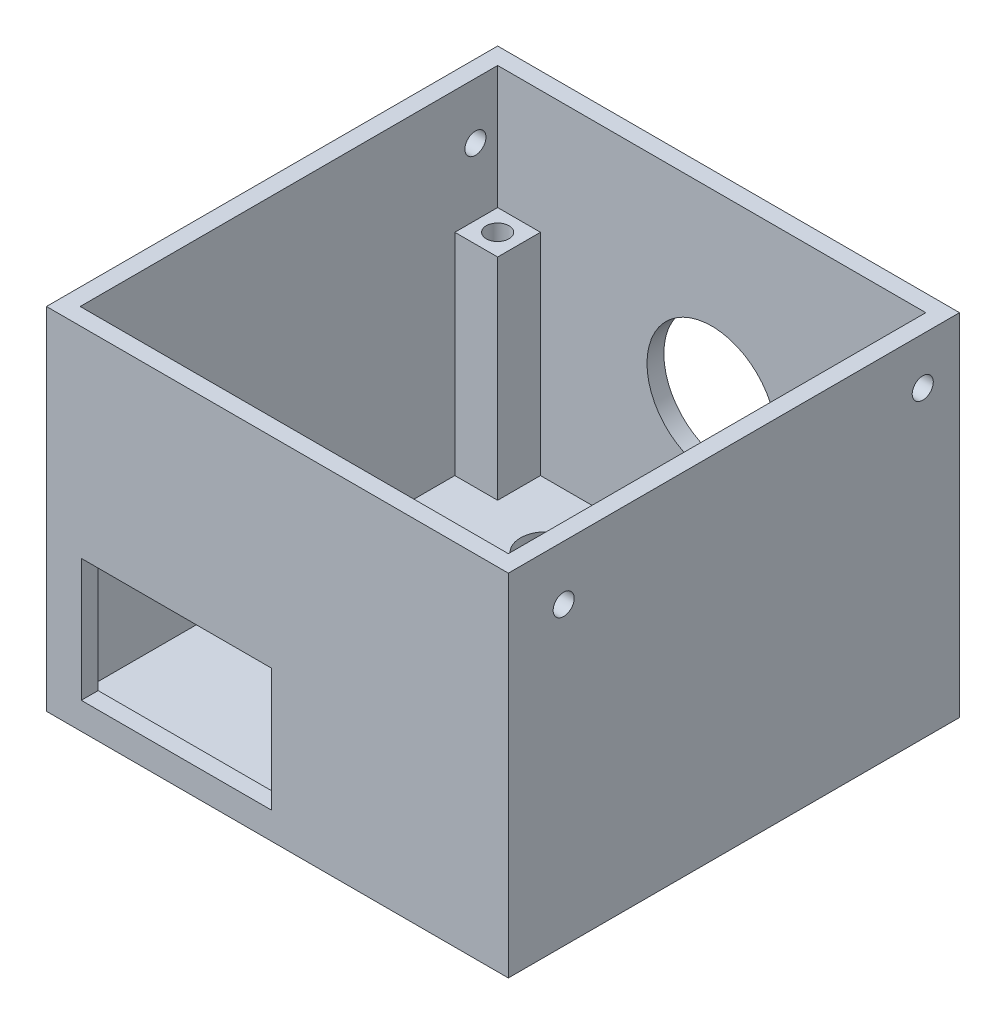
SolidWorks part; units mm, degrees
ref_plane "Front Plane" through (0, 0, 0) normal (0, 0, 1) x (1, 0, 0)
ref_plane "Top Plane" through (0, 0, 0) normal (0, 1, 0) x (1, 0, 0)
ref_plane "Right Plane" through (0, 0, 0) normal (1, 0, 0) x (0, 0, -1)
sketch "Sketch1" plane through (0, 0, 0) normal (0, 1, 0) x (1, 0, 0)
  line L1 (27.4, -26.765) -> (-27.4, -26.765)
  line L2 (27.4, -26.765) -> (27.4, 26.765)
  line L3 (27.4, 26.765) -> (-27.4, 26.765)
  line L4 (-27.4, -26.765) -> (-27.4, 26.765)
  line L5 (27.4, -26.765) -> (-27.4, 26.765) construction
  line L6 (27.4, 26.765) -> (-27.4, -26.765) construction
  point P0 (0, 0)
  dimension "D1" = 54.8
  dimension "D2" = 53.53
extrude "Boss-Extrude1" add sketch "Sketch1" along normal blind 41.6
sketch "Sketch2" plane through (0, 41.6, 0) normal (0, 1, 0) x (1, 0, 0)
  line L0 (-27.4, 26.765) -> (-27.4, -26.765) construction
  line L1 (25.4, -24.765) -> (-25.4, -24.765)
  line L2 (25.4, -24.765) -> (25.4, 24.765)
  line L3 (25.4, 24.765) -> (-25.4, 24.765)
  line L4 (-25.4, -24.765) -> (-25.4, 24.765)
  line L5 (25.4, -24.765) -> (-25.4, 24.765) construction
  line L6 (25.4, 24.765) -> (-25.4, -24.765) construction
  line L7 (27.4, 26.765) -> (-27.4, 26.765) construction
  point P0 (0, 0)
  dimension "D1" = 2
  dimension "D2" = 2
extrude "Cut-Extrude1" cut sketch "Sketch2" against normal blind 39.6
sketch "Sketch3" plane through (0, 2, 0) normal (0, 1, 0) x (1, 0, 0)
  line L1 (-25.4, 24.765) -> (-20.32, 24.765)
  line L2 (-25.4, 24.765) -> (-25.4, 19.685)
  line L3 (-25.4, 19.685) -> (-20.32, 19.685)
  line L4 (-20.32, 24.765) -> (-20.32, 19.685)
  line L5 (25.4, 24.765) -> (20.32, 24.765)
  line L6 (25.4, 24.765) -> (25.4, 19.685)
  line L7 (25.4, 19.685) -> (20.32, 19.685)
  line L8 (20.32, 24.765) -> (20.32, 19.685)
  line L9 (25.4, -24.765) -> (20.32, -24.765)
  line L10 (25.4, -24.765) -> (25.4, -19.685)
  line L11 (25.4, -19.685) -> (20.32, -19.685)
  line L12 (20.32, -24.765) -> (20.32, -19.685)
  dimension "D1" = 5.08
  dimension "D2" = 5.08
  dimension "D3" = 5.08
  dimension "D4" = 5.08
  dimension "D5" = 5.08
  dimension "D6" = 5.08
extrude "Boss-Extrude2" add sketch "Sketch3" along normal blind 25
sketch "Sketch4" plane through (0, 27, 0) normal (0, 1, 0) x (1, 0, 0)
  line L0 (-20.32, 19.685) -> (-20.32, 24.765) construction
  line L3 (-25.4, 19.685) -> (-20.32, 19.685) construction
  line L4 (20.32, 19.685) -> (25.4, 19.685) construction
  line L5 (20.32, 24.765) -> (20.32, 19.685) construction
  line L6 (25.4, -19.685) -> (20.32, -19.685) construction
  line L7 (20.32, -19.685) -> (20.32, -24.765) construction
  circle A0 centre (-22.86, 22.225) radius 1.35
  circle A1 centre (22.86, 22.225) radius 1.35
  circle A2 centre (22.86, -22.225) radius 1.35
  point P12 (22.86, -19.685)
  dimension "D1" = 2.54
  dimension "D3" = 2.54
  dimension "D5" = 2.54
  dimension "D2" = 2.54
  dimension "D4" = 2.54
  dimension "D6" = 2.54
extrude "Cut-Extrude2" cut sketch "Sketch4" against normal blind 10
sketch "Sketch5" plane through (0, 0, 0) normal (0, -1, 0) x (-1, 0, 0)
  circle A0 centre (-12.7629, 17.1869) radius 3
  circle A1 centre (12.1084, 17.1869) radius 3
extrude "Cut-Extrude3" cut sketch "Sketch5" against normal up to next
sketch "Sketch6" plane through (0, 0, 0) normal (0, -1, 0) x (-1, 0, 0)
  circle A0 centre (-16.7643, 3.6231) radius 2
  circle A1 centre (-16.7643, -2.0736) radius 2
extrude "Cut-Extrude4" cut sketch "Sketch6" against normal up to next
sketch "Sketch7" plane through (0, 0, 0) normal (0, -1, 0) x (-1, 0, 0)
  circle A0 centre (-16.6778, -12.0076) radius 3.6
extrude "Cut-Extrude5" cut sketch "Sketch7" against normal up to next
sketch "Sketch8" plane through (27.4, 0, 0) normal (1, 0, 0) x (0, 0, -1)
  circle A0 centre (-20.2009, 35.1133) radius 1.25
extrude "Cut-Extrude6" cut sketch "Sketch8" against normal up to next
sketch "Sketch10" plane through (-27.4, 0, 0) normal (-1, 0, 0) x (0, 0, 1)
  circle A0 centre (-22.1268, 34.9354) radius 1.25
extrude "Cut-Extrude7" cut sketch "Sketch10" against normal up to next
sketch "Sketch12" plane through (0, 0, -26.765) normal (0, 0, -1) x (-1, 0, 0)
  circle A0 centre (0, 19.8508) radius 7.6805
extrude "Cut-Extrude8" cut sketch "Sketch12" against normal up to next
sketch "Sketch13" plane through (0, 0, 26.765) normal (0, 0, 1) x (1, 0, 0)
  line L1 (-0.6897, 3.1964) -> (-23.2715, 3.1964)
  line L2 (-0.6897, 3.1964) -> (-0.6897, 17.7861)
  line L3 (-0.6897, 17.7861) -> (-23.2715, 17.7861)
  line L4 (-23.2715, 3.1964) -> (-23.2715, 17.7861)
  line L5 (-0.6897, 3.1964) -> (-23.2715, 17.7861) construction
  line L6 (-0.6897, 17.7861) -> (-23.2715, 3.1964) construction
  point P0 (-11.9806, 10.4912)
extrude "Cut-Extrude9" cut sketch "Sketch13" against normal up to next
sketch "Sketch14" plane through (27.4, 0, 0) normal (1, 0, 0) x (0, 0, -1)
  circle A0 centre (22.4032, 36.0407) radius 1.25
extrude "Cut-Extrude10" cut sketch "Sketch14" against normal up to next
